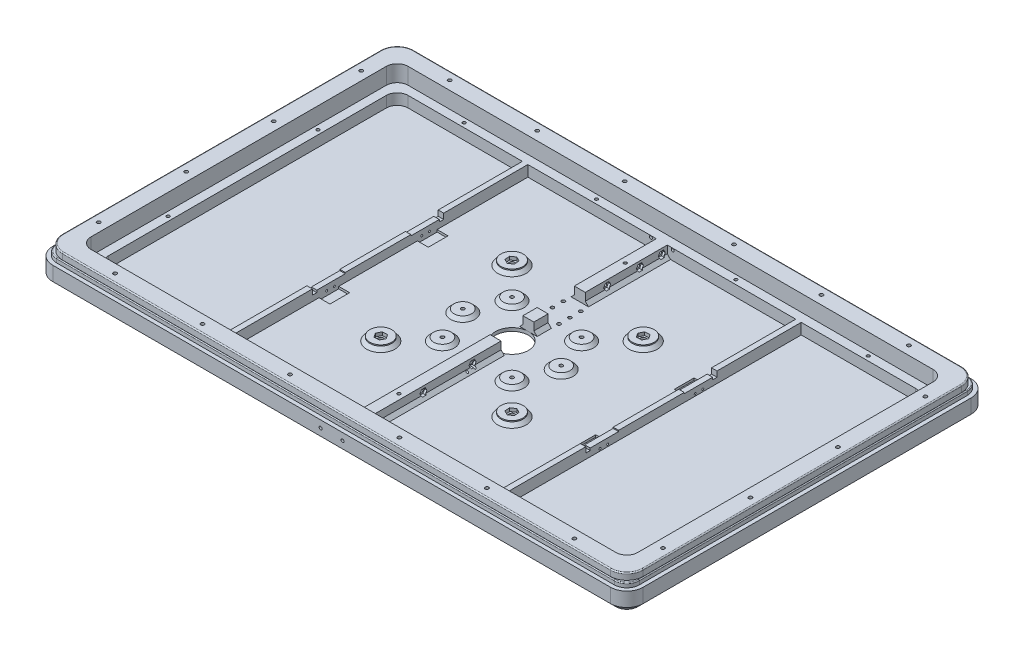
SolidWorks part; units mm, degrees
ref_plane "Front Plane" through (0, 0, 0) normal (0, 0, 1) x (1, 0, 0)
ref_plane "Top Plane" through (0, 0, 0) normal (0, 1, 0) x (1, 0, 0)
ref_plane "Right Plane" through (0, 0, 0) normal (1, 0, 0) x (0, 0, -1)
sketch "Sketch1" plane through (0, 0, 0) normal (0, 1, 0) x (1, 0, 0)
  line L1 (-270, -165) -> (270, -165)
  line L2 (-270, -165) -> (-270, 165)
  line L3 (-270, 165) -> (270, 165)
  line L4 (270, -165) -> (270, 165)
  line L5 (-270, -165) -> (270, 165) construction
  line L6 (-270, 165) -> (270, -165) construction
  point P0 (0, 0)
  dimension "D1" = 540
  dimension "D2" = 330
extrude "Boss-Extrude1" add sketch "Sketch1" along normal blind 3
sketch "Sketch2" plane through (0, 3, 0) normal (0, 1, 0) x (1, 0, 0)
  line L0 (250, 145) -> (-250, 145)
  line L1 (270, -165) -> (-270, -165)
  line L2 (270, -165) -> (270, 165)
  line L3 (270, 165) -> (-270, 165)
  line L4 (-270, -165) -> (-270, 165)
  line L5 (270, -165) -> (-270, 165) construction
  line L6 (270, 165) -> (-270, -165) construction
  line L7 (-250, -145) -> (-250, 145)
  line L8 (250, -145) -> (-250, -145)
  line L9 (250, -145) -> (250, 145)
  point P0 (0, 0)
  dimension "D1" = 20
  dimension "D2" = 540
extrude "Boss-Extrude2" add sketch "Sketch2" along normal blind 25 contours L0 L7 L8 L9 | L2 L1 L4 L3
fillet "Fillet1" radius 15 4 edges at (-270, 14, -165) (-270, 14, 165) (270, 14, 165) (270, 14, -165)
sketch "Sketch4" plane through (0, 28, 0) normal (0, 1, 0) x (1, 0, 0)
  line L0 (-270, 0) -> (-258, 0) construction
  line L1 (-270, -150) -> (-270, 150) construction
  line L2 (-258, 0) -> (-258, 40) construction
  line L3 (-258, 40) -> (-258, 120) construction
  line L4 (0, 0) -> (0, 145) construction
  line L5 (250, 145) -> (-250, 145) construction
  line L6 (0, 165) -> (0, 153) construction
  line L7 (255, 165) -> (-255, 165) construction
  line L8 (0, 153) -> (-50, 153) construction
  line L9 (-50, 153) -> (-130, 153) construction
  line L10 (-130, 153) -> (-210, 153) construction
  line L11 (130, 153) -> (210, 153) construction
  line L12 (50, 153) -> (130, 153) construction
  line L13 (258, 40) -> (258, 120) construction
  line L14 (0, 0) -> (78.1952, 0) construction
  line L15 (258, -40) -> (258, -120) construction
  line L16 (50, -153) -> (130, -153) construction
  line L17 (130, -153) -> (210, -153) construction
  line L18 (-130, -153) -> (-210, -153) construction
  line L19 (-50, -153) -> (-130, -153) construction
  line L20 (0, -153) -> (-50, -153) construction
  line L21 (0, -165) -> (0, -153) construction
  line L22 (-258, -40) -> (-258, -120) construction
  circle A0 centre (-258, 120) radius 1.6
  circle A1 centre (-258, 40) radius 1.6
  circle A2 centre (-210, 153) radius 1.6
  circle A3 centre (-130, 153) radius 1.6
  circle A4 centre (-50, 153) radius 1.6
  circle A5 centre (50, 153) radius 1.6
  circle A6 centre (130, 153) radius 1.6
  circle A7 centre (210, 153) radius 1.6
  circle A8 centre (258, 40) radius 1.6
  circle A9 centre (258, 120) radius 1.6
  circle A10 centre (258, -120) radius 1.6
  circle A11 centre (258, -40) radius 1.6
  circle A12 centre (210, -153) radius 1.6
  circle A13 centre (130, -153) radius 1.6
  circle A14 centre (50, -153) radius 1.6
  circle A15 centre (-50, -153) radius 1.6
  circle A16 centre (-130, -153) radius 1.6
  circle A17 centre (-210, -153) radius 1.6
  circle A18 centre (-258, -40) radius 1.6
  circle A19 centre (-258, -120) radius 1.6
  dimension "D1" = 50
  dimension "D2" = 80
  dimension "D3" = 80
  dimension "D4" = 12
  dimension "D5" = 12
  dimension "D6" = 40
  dimension "D7" = 80
extrude "Cut-Extrude1" cut sketch "Sketch4" against normal up to surface (28 mm away) up to face at (0, 0, 0)
sketch "Sketch5" plane through (0, 3, 0) normal (0, 1, 0) x (1, 0, 0)
  circle A0 centre (0, 0) radius 15
  dimension "D1" = 30
extrude "Cut-Extrude2" cut sketch "Sketch5" against normal up to surface (3 mm away) up to face at (-130, 0, 151.4)
chamfer "Chamfer1" distance 5 angle 45 8 edges at (270, 0, 0) (0, 0, -165) (0, 0, 165) (265.6066, 0, -160.6066) (265.6066, 0, 160.6066) (-265.6066, 0, -160.6066) (-265.6066, 0, 160.6066) (-270, 0, 0)
sketch "Sketch7" plane through (0, 0, 0) normal (0, -1, 0) x (1, 0, 0)
  line L1 (-60, -60) -> (60, -60) construction
  line L2 (-60, -60) -> (-60, 60) construction
  line L3 (-60, 60) -> (60, 60) construction
  line L4 (60, -60) -> (60, 60) construction
  line L5 (-60, -60) -> (60, 60) construction
  line L6 (-60, 60) -> (60, -60) construction
  circle A0 centre (-60, 60) radius 2.6
  circle A1 centre (60, 60) radius 2.6
  circle A2 centre (60, -60) radius 2.6
  circle A3 centre (-60, -60) radius 2.6
  point P0 (0, 0)
  dimension "D1" = 120
  dimension "D2" = 120
extrude "Cut-Extrude3" cut sketch "Sketch7" against normal up to surface (3 mm away) up to face at (0, 3, 15)
sketch "Sketch9" plane through (0, 0, 0) normal (0, -1, 0) x (1, 0, 0)
  line L0 (0, 0) -> (45, 0) construction
  line L1 (-31.8198, -31.8198) -> (31.8198, -31.8198) construction
  line L2 (-31.8198, -31.8198) -> (-31.8198, 31.8198) construction
  line L3 (-31.8198, 31.8198) -> (31.8198, 31.8198) construction
  line L4 (31.8198, -31.8198) -> (31.8198, 31.8198) construction
  line L5 (-31.8198, -31.8198) -> (31.8198, 31.8198) construction
  line L6 (-31.8198, 31.8198) -> (31.8198, -31.8198) construction
  line L7 (0, 0) -> (0, -31.8198) construction
  circle A0 centre (-31.8198, 31.8198) radius 1.6
  circle A1 centre (31.8198, 31.8198) radius 1.6
  circle A2 centre (31.8198, -31.8198) radius 1.6
  circle A3 centre (-31.8198, -31.8198) radius 1.6
  circle A4 centre (45, 0) radius 1.6
  circle A5 centre (-45, 0) radius 1.6
  point P0 (0, 0)
  dimension "D3" = 45
  dimension "D1" = 90
  dimension "D2" = 90
extrude "Cut-Extrude4" cut sketch "Sketch9" against normal blind 47
sketch "Sketch17" plane through (0, 28, 0) normal (0, 1, 0) x (1, 0, 0)
  line L0 (0, 0) -> (0, 165) construction
  line L1 (265, 165) -> (-265, 165) construction
sketch "Sketch18" plane through (0, 28, 0) normal (0, 1, 0) x (1, 0, 0)
  line L0 (0, 165) -> (0, -165) construction
  line L1 (265, 165) -> (-265, 165) construction
  line L2 (265, -165) -> (-265, -165) construction
sketch "Sketch19" plane through (0, 28, 0) normal (0, 1, 0) x (1, 0, 0)
  line L0 (250.5, 160.5) -> (-250.5, 160.5)
  line L1 (255, -165) -> (-255, -165)
  line L2 (270, -150) -> (270, 150)
  line L3 (255, 165) -> (-255, 165)
  line L4 (-270, -150) -> (-270, 150)
  line L5 (270, -165) -> (-270, 165) construction
  line L6 (270, 165) -> (-270, -165) construction
  line L7 (-265.5, -145.5) -> (-265.5, 145.5)
  line L8 (250.5, -160.5) -> (-250.5, -160.5)
  line L9 (265.5, -145.5) -> (265.5, 145.5)
  line L10 (255, 160.5) -> (-255, 160.5) construction
  line L11 (-265.5, -150) -> (-265.5, 150) construction
  line L12 (265.5, -150) -> (265.5, 150) construction
  line L13 (255, -160.5) -> (-255, -160.5) construction
  arc A0 (-270, -150) -> (-255, -165) centre (-255, -150) ccw
  arc A1 (255, -165) -> (270, -150) centre (255, -150) ccw
  arc A2 (270, 150) -> (255, 165) centre (255, 150) ccw
  arc A3 (-255, 165) -> (-270, 150) centre (-255, 150) ccw
  arc A4 (-255, 160.5) -> (-265.5, 150) centre (-255, 150) ccw construction
  arc A5 (-265.5, -150) -> (-255, -160.5) centre (-255, -150) ccw construction
  arc A6 (255, -160.5) -> (265.5, -150) centre (255, -150) ccw construction
  arc A7 (265.5, 150) -> (255, 160.5) centre (255, 150) ccw construction
  arc A8 (-250.5, 160.5) -> (-265.5, 145.5) centre (-250.5, 145.5) ccw
  arc A9 (265.5, 145.5) -> (250.5, 160.5) centre (250.5, 145.5) ccw
  arc A10 (265.5, -145.5) -> (250.5, -160.5) centre (250.5, -145.5) cw
  arc A11 (-250.5, -160.5) -> (-265.5, -145.5) centre (-250.5, -145.5) cw
  point P0 (0, 0)
  dimension "D3" = 15
  dimension "D5" = 15
  dimension "D6" = 15
  dimension "D7" = 15
  dimension "D8" = 15
  dimension "D1" = 330
  dimension "D2" = 540
  dimension "D4" = 4.5
extrude "Cut-Extrude5" cut sketch "Sketch19" against normal blind 10
fillet "Fillet2" radius 1 8 edges at (265.5, 28, 0) (0, 28, 160.5) (-265.5, 28, 0) (0, 28, -160.5) (261.1066, 28, -156.1066) (261.1066, 28, 156.1066) (-261.1066, 28, 156.1066) (-261.1066, 28, -156.1066)
sketch "Sketch20" plane through (0, 18, 0) normal (0, 1, 0) x (1, 0, 0)
  line L0 (0, 165) -> (0, -165) construction
  line L1 (-255, 165) -> (255, 165) construction
  line L2 (-270, 150) -> (-270, -150) construction
  line L3 (-255, -165) -> (255, -165) construction
  line L4 (270, 150) -> (270, -150) construction
  line L5 (-270, 165) -> (270, -165) construction
  line L6 (-270, -165) -> (270, 165) construction
  line L7 (-255, 161.4) -> (255, 161.4)
  line L8 (266.4, 150) -> (266.4, -150)
  line L9 (-255, -161.4) -> (255, -161.4)
  line L10 (-266.4, 150) -> (-266.4, -150)
  line L11 (-255, 157.9) -> (255, 157.9)
  line L12 (262.9, 150) -> (262.9, -150)
  line L13 (-255, -157.9) -> (255, -157.9)
  line L14 (-262.9, 150) -> (-262.9, -150)
  arc A0 (-270, -150) -> (-255, -165) centre (-255, -150) ccw construction
  arc A1 (270, -150) -> (255, -165) centre (255, -150) cw construction
  arc A2 (270, 150) -> (255, 165) centre (255, 150) ccw construction
  arc A3 (-255, 165) -> (-270, 150) centre (-255, 150) ccw construction
  arc A4 (266.4, 150) -> (255, 161.4) centre (255, 150) ccw
  arc A5 (266.4, -150) -> (255, -161.4) centre (255, -150) cw
  arc A6 (-266.4, -150) -> (-255, -161.4) centre (-255, -150) ccw
  arc A7 (-255, 161.4) -> (-266.4, 150) centre (-255, 150) ccw
  arc A8 (262.9, 150) -> (255, 157.9) centre (255, 150) ccw
  arc A9 (262.9, -150) -> (255, -157.9) centre (255, -150) cw
  arc A10 (-262.9, -150) -> (-255, -157.9) centre (-255, -150) ccw
  arc A11 (-255, 157.9) -> (-262.9, 150) centre (-255, 150) ccw
  point P0 (0, 0)
  dimension "D3" = 15
  dimension "D1" = 330
  dimension "D2" = 540
  dimension "D4" = 3.6
  dimension "D5" = 3.5
extrude "Boss-Extrude3" add sketch "Sketch20" along normal blind 4
fillet "Fillet4" radius 0.8 8 edges at (263.061, 22, -158.061) (266.4, 22, 0) (263.061, 22, 158.061) (0, 22, 161.4) (-263.061, 22, 158.061) (-266.4, 22, 0) (-263.061, 22, -158.061) (0, 22, -161.4)
sketch "Sketch23" plane through (0, 3, 0) normal (0, 1, 0) x (1, 0, 0)
  line L0 (250, 145) -> (-250, 145) construction
  line L1 (-5, -145) -> (5, -145)
  line L2 (-5, -145) -> (-5, 145)
  line L3 (-5, 145) -> (5, 145)
  line L4 (5, -145) -> (5, 145)
  line L5 (-5, -145) -> (5, 145) construction
  line L6 (-5, 145) -> (5, -145) construction
  line L7 (0, 0) -> (250, 0) construction
  line L8 (-5, -15) -> (5, -15)
  line L9 (-5, -15) -> (-5, 15)
  line L10 (-5, 15) -> (5, 15)
  line L11 (5, -15) -> (5, 15)
  line L12 (-5, -15) -> (5, 15) construction
  line L13 (-5, 15) -> (5, -15) construction
  line L14 (250, -145) -> (250, 145) construction
  line L15 (250, 145) -> (-250, 145) construction
  line L16 (122.5, -145) -> (127.5, -145)
  line L17 (122.5, -145) -> (122.5, 145)
  line L18 (122.5, 145) -> (127.5, 145)
  line L19 (127.5, -145) -> (127.5, 145)
  line L20 (122.5, -145) -> (127.5, 145) construction
  line L21 (122.5, 145) -> (127.5, -145) construction
  line L27 (0, 0) -> (0, 145) construction
  line L28 (-122.5, 145) -> (-127.5, 145)
  line L29 (-127.5, -145) -> (-127.5, 145)
  line L30 (-122.5, -145) -> (-127.5, -145)
  line L31 (-122.5, -145) -> (-122.5, 145)
  point P0 (0, 0)
  point P8 (0, 0)
  point P17 (125, 0)
  line M14 (-250, -145) -> (250, -145)
  line M16 (250, 145) -> (-250, 145)
  dimension "D1" = 30
  dimension "D2" = 10
  dimension "D3" = 5
extrude "Boss-Extrude4" add sketch "Sketch23" along normal blind 10 contours L2 L10 L4 M16 | L8 L2 L4 M14 | L17 L16 L19 L18 | L28 L29 L30 L31 region at (0, 3, 80) region at (0, 3, -80)
sketch "Sketch24" plane through (0, 3, 0) normal (0, 1, 0) x (1, 0, 0)
  line L0 (-242, 137) -> (242, 137)
  line L1 (-250, -145) -> (250, -145)
  line L2 (-250, -145) -> (-250, 145)
  line L3 (-250, 145) -> (250, 145)
  line L4 (250, -145) -> (250, 145)
  line L5 (-250, -145) -> (250, 145) construction
  line L6 (-250, 145) -> (250, -145) construction
  line L7 (242, -137) -> (242, 137)
  line L8 (-242, -137) -> (242, -137)
  line L9 (-242, -137) -> (-242, 137)
  point P0 (0, 0)
  dimension "D1" = 8
extrude "Boss-Extrude5" add sketch "Sketch24" along normal up to surface (10 mm away) up to face at (-125, 13, 0)
sketch "Sketch25" plane through (127.5, 0, 0) normal (1, 0, 0) x (0, 0, -1)
  line L0 (0, 5) -> (0, 13) construction
  line L1 (-150, 5) -> (150, 5) construction
  line L2 (-145, 13) -> (145, 13) construction
  line L3 (0, 13) -> (0, 5) construction
  line L4 (0, 5) -> (-40, 5) construction
  line L5 (-40, 5) -> (-47, 5) construction
  circle A0 centre (-47, 5) radius 0.9
  circle A1 centre (-40, 5) radius 0.9
  circle A2 centre (47, 5) radius 0.9
  circle A3 centre (40, 5) radius 0.9
  dimension "D1" = 8
  dimension "D2" = 40
  dimension "D3" = 7
extrude "Cut-Extrude6" cut sketch "Sketch25" against normal up to surface (255 mm away) up to face at (-127.5, 8, 0)
sketch "Sketch26" plane through (0, 3, 0) normal (0, 1, 0) x (1, 0, 0)
  line L0 (0, 0) -> (-122.5, 0) construction
  line L1 (-122.5, -137) -> (-122.5, 137) construction
  line L2 (-122.5, 0) -> (-122.5, 36) construction
  line L3 (-122.5, -137) -> (-122.5, 137) construction
  line L4 (-122.5, -54) -> (-112.5, -54)
  line L5 (-122.5, 36) -> (-112.5, 36)
  line L6 (-122.5, 36) -> (-122.5, 54)
  line L7 (-122.5, 54) -> (-112.5, 54)
  line L8 (-112.5, 36) -> (-112.5, 54)
  line L9 (-122.5, -36) -> (-112.5, -36)
  line L10 (-122.5, -36) -> (-122.5, -54)
  line L11 (-112.5, -36) -> (-112.5, -54)
  line L12 (0, 0) -> (0, 165) construction
  line L13 (122.5, -36) -> (122.5, -54)
  line L14 (122.5, -36) -> (112.5, -36)
  line L15 (112.5, -36) -> (112.5, -54)
  line L16 (122.5, -54) -> (112.5, -54)
  line L17 (122.5, 54) -> (112.5, 54)
  line L18 (112.5, 36) -> (112.5, 54)
  line L19 (122.5, 36) -> (112.5, 36)
  line L20 (122.5, 36) -> (122.5, 54)
  point P11 (-112.5, 45)
  dimension "D1" = 36
  dimension "D2" = 10
extrude "Cut-Extrude7" cut sketch "Sketch26" against normal blind 2
sketch "Sketch27" plane through (0, 13, 0) normal (0, 1, 0) x (1, 0, 0)
  line L0 (0, 0) -> (0, 165) construction
  line L1 (-122.5, 0) -> (-127.5, 0) construction
  line L2 (-122.5, -36) -> (-122.5, 36) construction
  line L3 (-127.5, -137) -> (-127.5, 137) construction
  line L4 (-127.5, -137) -> (-127.5, 137) construction
  line L5 (-122.5, -60) -> (-127.5, -60)
  line L6 (-122.5, -60) -> (-122.5, -30)
  line L7 (-122.5, 60) -> (-127.5, 60)
  line L8 (-127.5, -60) -> (-127.5, -30)
  line L9 (-122.5, -60) -> (-123.75, -30) construction
  line L10 (-122.5, 60) -> (-123.75, 30) construction
  line L11 (-127.5, 30) -> (-127.5, 60)
  line L12 (-127.5, -30) -> (-122.5, -30)
  line L14 (-127.5, 30) -> (-122.5, 30)
  line L16 (126.25, -30) -> (127.5, -60) construction
  line L17 (126.25, 30) -> (127.5, 60) construction
  line L18 (-126.25, 30) -> (-127.5, 60) construction
  line L19 (-126.25, -30) -> (-127.5, -60) construction
  line L20 (-122.5, 30) -> (-122.5, 60)
  line L21 (122.5, 60) -> (123.75, 30) construction
  line L22 (122.5, -60) -> (123.75, -30) construction
  line L23 (122.5, 0) -> (127.5, 0) construction
  line L24 (122.5, 30) -> (122.5, 60)
  line L25 (127.5, 30) -> (122.5, 30)
  line L26 (127.5, -30) -> (122.5, -30)
  line L27 (127.5, 30) -> (127.5, 60)
  line L28 (127.5, -60) -> (127.5, -30)
  line L29 (122.5, 60) -> (127.5, 60)
  line L30 (122.5, -60) -> (122.5, -30)
  line L31 (122.5, -60) -> (127.5, -60)
  point P10 (-125, 0)
  point P17 (-125, 0)
  point P40 (125, 0)
  dimension "D1" = 120
  dimension "D2" = 60
extrude "Cut-Extrude8" cut sketch "Sketch27" against normal blind 3
sketch "Sketch28" plane through (0, 13, 0) normal (0, 1, 0) x (1, 0, 0)
  line L1 (-127.5, 30) -> (-122.5, 30)
  line L2 (-127.5, 30) -> (-127.5, -30)
  line L3 (-127.5, -30) -> (-122.5, -30)
  line L4 (-122.5, 30) -> (-122.5, -30)
  line L5 (122.5, 30) -> (127.5, 30)
  line L6 (122.5, 30) -> (122.5, -30)
  line L7 (122.5, -30) -> (127.5, -30)
  line L8 (127.5, 30) -> (127.5, -30)
extrude "Cut-Extrude9" cut sketch "Sketch28" against normal blind 2
sketch "Sketch29" plane through (0, 10, 0) normal (0, 1, 0) x (1, 0, 0)
  line L0 (-122.5, 30) -> (-122.5, 60) construction
  line L1 (-127.5, 60) -> (-122.5, 60)
  line L2 (-127.5, 60) -> (-127.5, 56)
  line L3 (-127.5, 56) -> (-122.5, 56)
  line L4 (-122.5, 60) -> (-122.5, 56)
  line L5 (-122.5, -60) -> (-122.5, -30) construction
  line L6 (-127.5, -60) -> (-122.5, -60)
  line L7 (-127.5, -60) -> (-127.5, -56)
  line L8 (-127.5, -56) -> (-122.5, -56)
  line L9 (-122.5, -60) -> (-122.5, -56)
  line L10 (127.5, -60) -> (127.5, -30) construction
  line L11 (122.5, -60) -> (127.5, -60)
  line L12 (122.5, -60) -> (122.5, -56)
  line L13 (122.5, -56) -> (127.5, -56)
  line L14 (127.5, -60) -> (127.5, -56)
  line L15 (127.5, -137) -> (127.5, 137) construction
  line L16 (122.5, 60) -> (127.5, 60)
  line L17 (122.5, 60) -> (122.5, 56)
  line L18 (122.5, 56) -> (127.5, 56)
  line L19 (127.5, 60) -> (127.5, 56)
extrude "Cut-Extrude10" cut sketch "Sketch29" against normal blind 2
sketch "Sketch31" plane through (0, 13, 0) normal (0, 1, 0) x (1, 0, 0)
  line L0 (0, 165) -> (0, 45) construction
  line L1 (255, 165) -> (-255, 165) construction
  line L3 (-8, 62) -> (8, 62)
  line L4 (-8, 62) -> (-8, 28)
  line L5 (-8, 28) -> (8, 28)
  line L6 (8, 62) -> (8, 28)
  line L7 (-8, 62) -> (8, 28) construction
  line L8 (-8, 28) -> (8, 62) construction
  dimension "D1" = 120
  dimension "D2" = 34
  dimension "D3" = 16
  dimension "D4" = 16
sketch "Sketch32" plane through (-270, 0, 0) normal (-1, 0, 0) x (0, 0, 1)
  line L0 (-30, 13) -> (-30, 18) construction
  line L1 (-62, 13) -> (-28, 13) construction
  line L2 (-150, 18) -> (150, 18) construction
  line L3 (-30, 18) -> (-30, 51) construction
extrude "Boss-Extrude6" add sketch "Sketch31" along normal blind 53 and the other way up to surface (10 mm away) other way up to face at (-60, 3, 57.4)
fillet "Fillet5" radius 15 2 edges at (0, 66, -28) (0, 66, -62)
sketch "Sketch34" plane through (-8, 0, 0) normal (-1, 0, 0) x (0, 0, 1)
  line L0 (-165, 18) -> (-45, 18) construction
  line L1 (-150, 18) -> (150, 18) construction
  line L2 (-45, 18) -> (-45, 53) construction
  circle A0 centre (-45, 53) radius 3
  dimension "D3" = 6
  dimension "D1" = 120
  dimension "D2" = 35
extrude "Cut-Extrude11" cut sketch "Sketch34" against normal blind 53
sketch "Sketch35" plane through (0, 3, 0) normal (0, 1, 0) x (1, 0, 0)
  circle A0 centre (-31.8198, 31.8198) radius 1.6
  circle A1 centre (-31.8198, 31.8198) radius 8
  circle A2 centre (31.8198, 31.8198) radius 1.6
  circle A3 centre (31.8198, 31.8198) radius 8
  circle A4 centre (31.8198, -31.8198) radius 1.6
  circle A5 centre (31.8198, -31.8198) radius 8
  circle A6 centre (-31.8198, -31.8198) radius 1.6
  circle A7 centre (-31.8198, -31.8198) radius 8
  circle A8 centre (-45, 0) radius 8
  circle A9 centre (45, 0) radius 8
  circle A10 centre (45, 0) radius 1.6
  circle A11 centre (-45, 0) radius 1.6
  point P16 (0, 0)
  dimension "D1" = 16
  dimension "D2" = 3.2
  dimension "D3" = 4
extrude "Boss-Extrude7" add sketch "Sketch35" along normal blind 3
chamfer "Chamfer2" distance 3 angle 45 6 edges at (31.8198, 3, 23.8198) (-31.8198, 3, 23.8198) (-31.8198, 3, -39.8198) (31.8198, 3, -39.8198) (45, 3, -8) (-45, 3, -8)
sketch "Sketch37" plane through (0, 66, 0) normal (0, 1, 0) x (1, 0, 0)
  line L0 (0, 47) -> (0, 43) construction
  line L1 (8, 47) -> (-8, 47) construction
  line L2 (-8, 43) -> (8, 43) construction
  line L4 (-8, 28) -> (8, 28)
  line L5 (-8, 28) -> (-8, 62)
  line L6 (-8, 62) -> (8, 62)
  line L7 (8, 28) -> (8, 62)
  line L8 (-8, 28) -> (8, 62) construction
  line L9 (-8, 62) -> (8, 28) construction
  point P6 (0, 45)
extrude "Cut-Extrude12" cut sketch "Sketch37" against normal up to surface (63 mm away) up to face at (-45, 3, -11)
sketch "Sketch38" plane through (0, 3, 0) normal (0, 1, 0) x (1, 0, 0)
  line L0 (0, 62) -> (0, 28) construction
  line L1 (5, 62) -> (-5, 62) construction
  line L2 (-5, 28) -> (5, 28) construction
  line L3 (0, 28) -> (0, 45) construction
  line L4 (0, 45) -> (8, 45) construction
  line L5 (8, 45) -> (8, 55) construction
  circle A0 centre (8, 55) radius 1.6
  circle A1 centre (8, 35) radius 1.6
  circle A2 centre (-8, 35) radius 1.6
  circle A3 centre (-8, 55) radius 1.6
  circle A4 centre (8, 45) radius 1.5
  circle A5 centre (-8, 45) radius 1.5
  dimension "D2" = 10
  dimension "D1" = 8
extrude "Cut-Extrude13" cut sketch "Sketch38" against normal blind 90
chamfer "Chamfer3" distance 3 angle 45 6 edges at (-5, 3, 76) (-5, 3, -21.5) (5, 3, -21.5) (5, 3, 76) (5, 3, -99.5) (-5, 3, -99.5)
sketch "Sketch39" plane through (0, 13, 0) normal (0, 1, 0) x (1, 0, 0)
  line L0 (-242, 0) -> (-242, 137) construction
  line L1 (-242, 137) -> (-242, -137) construction
  line L2 (-242, 137) -> (-242, 68.5) construction
  line L3 (-242, 68.5) -> (-250, 68.5) construction
  line L4 (-250, -145) -> (-250, 145) construction
  line L5 (-184.75, 137) -> (-184.75, 145) construction
  line L6 (-127.5, 137) -> (-242, 137) construction
  line L7 (250, 145) -> (-250, 145) construction
  line L8 (-63.75, 137) -> (-63.75, 145) construction
  line L10 (-5, 137) -> (-122.5, 137) construction
  line L11 (250, 145) -> (-250, 145) construction
  line L12 (0, 0) -> (0, 145) construction
  line L13 (63.75, 137) -> (63.75, 145) construction
  line L14 (184.75, 137) -> (184.75, 145) construction
  line L15 (242, 68.5) -> (250, 68.5) construction
  line L16 (242, 137) -> (242, 68.5) construction
  line L17 (0, 62) -> (0, 145) construction
  line L18 (5, 62) -> (-5, 62) construction
  line L19 (0, 0) -> (250, 0) construction
  line L20 (250, -145) -> (250, 145) construction
  line L21 (0, -62) -> (0, -145) construction
  line L22 (242, -137) -> (242, -68.5) construction
  line L23 (242, -68.5) -> (250, -68.5) construction
  line L24 (184.75, -137) -> (184.75, -145) construction
  line L25 (63.75, -137) -> (63.75, -145) construction
  line L26 (-63.75, -137) -> (-63.75, -145) construction
  line L27 (-184.75, -137) -> (-184.75, -145) construction
  line L28 (-242, -68.5) -> (-250, -68.5) construction
  line L29 (-242, -137) -> (-242, -68.5) construction
  circle A0 centre (-246, 68.5) radius 1.4
  circle A1 centre (-184.75, 141) radius 1.4
  circle A2 centre (-63.75, 141) radius 1.4
  circle A3 centre (63.75, 141) radius 1.4
  circle A4 centre (184.75, 141) radius 1.4
  circle A5 centre (246, 68.5) radius 1.4
  circle A6 centre (0, 103.5) radius 1.4
  circle A7 centre (0, -103.5) radius 1.4
  circle A8 centre (246, -68.5) radius 1.4
  circle A9 centre (184.75, -141) radius 1.4
  circle A10 centre (63.75, -141) radius 1.4
  circle A11 centre (-63.75, -141) radius 1.4
  circle A12 centre (-184.75, -141) radius 1.4
  circle A13 centre (-246, -68.5) radius 1.4
extrude "Cut-Extrude14" cut sketch "Sketch39" against normal blind 8
fillet "Fillet6" radius 10 4 edges at (-242, 8, -137) (-242, 8, 137) (242, 8, 137) (242, 8, -137)
fillet "Fillet7" radius 10 4 edges at (250, 20.5, 145) (250, 20.5, -145) (-250, 20.5, 145) (-250, 20.5, -145)
sketch "Sketch41" plane through (0, 0, 0) normal (1, 0, 0) x (0, 0, -1)
  line L0 (165, 11.5) -> (153, 11.5) construction
  line L1 (165, 18) -> (165, 5) construction
  line L2 (0, 0) -> (0, 98.4706) construction
  circle A0 centre (153, 11.5) radius 5
  circle A1 centre (-153, 11.5) radius 5
  dimension "D1" = 12
extrude "Cut-Extrude15" cut sketch "Sketch41" against normal blind 30 and the other way blind 30
sketch "Sketch42" plane through (5, 0, 0) normal (1, 0, 0) x (0, 0, -1)
  line L0 (-132, 3) -> (-132, 13) construction
  line L1 (-127, 3) -> (-137, 3) construction
  line L2 (-135, 13) -> (135, 13) construction
  line L3 (-102.1, 13) -> (-69.9, 13) construction
  line L4 (-69.9, 13) -> (-86, 13) construction
  line L5 (-86, 13) -> (-86, 3) construction
  line L6 (-127, 3) -> (127, 3) construction
  line L7 (-67.1, 13) -> (-15, 13) construction
  line L8 (-15, 13) -> (-41.05, 13) construction
  line L9 (-41.05, 13) -> (-41.05, 3) construction
  line L10 (145, 13) -> (145, 3) construction
  line L11 (145, 3) -> (145, 8) construction
  line L12 (145, 8) -> (132, 8) construction
  line L13 (132, 8) -> (112, 8) construction
  line L14 (112, 8) -> (82, 8) construction
  circle A0 centre (112, 8) radius 1.6
  circle A1 centre (132, 8) radius 1.6
  circle A2 centre (82, 8) radius 1.6
  circle A3 centre (-86, 8) radius 1.6
  circle A4 centre (-132, 8) radius 1.6
  circle A5 centre (-41.05, 8) radius 1.6
  dimension "D1" = 30
  dimension "D2" = 20
  dimension "D3" = 13
extrude "Cut-Extrude16" cut sketch "Sketch42" against normal blind 30 and the other way blind 10
sketch "Sketch43" plane through (5, 0, 0) normal (1, 0, 0) x (0, 0, -1)
  line L0 (-87.6166, 10.8) -> (-89.2332, 8)
  line L1 (-128.7668, 8) -> (-130.3834, 10.8)
  line L2 (-130.3834, 10.8) -> (-133.6166, 10.8)
  line L3 (-133.6166, 10.8) -> (-135.2332, 8)
  line L4 (-135.2332, 8) -> (-133.6166, 5.2)
  line L5 (-133.6166, 5.2) -> (-130.3834, 5.2)
  line L6 (-130.3834, 5.2) -> (-128.7668, 8)
  line L7 (-89.2332, 8) -> (-87.6166, 5.2)
  line L8 (-87.6166, 5.2) -> (-84.3834, 5.2)
  line L9 (-82.7668, 8) -> (-84.3834, 10.8)
  line L10 (-84.3834, 10.8) -> (-87.6166, 10.8)
  line L11 (-84.3834, 5.2) -> (-82.7668, 8)
  line L12 (-37.8168, 8) -> (-39.4334, 10.8)
  line L13 (-39.4334, 5.2) -> (-37.8168, 8)
  line L14 (-42.6666, 10.8) -> (-44.2832, 8)
  line L15 (-39.4334, 10.8) -> (-42.6666, 10.8)
  line L16 (-42.6666, 5.2) -> (-39.4334, 5.2)
  line L17 (-44.2832, 8) -> (-42.6666, 5.2)
  line L18 (85.2332, 8) -> (83.6166, 10.8)
  line L19 (83.6166, 5.2) -> (85.2332, 8)
  line L20 (80.3834, 10.8) -> (78.7668, 8)
  line L21 (83.6166, 10.8) -> (80.3834, 10.8)
  line L22 (80.3834, 5.2) -> (83.6166, 5.2)
  line L23 (78.7668, 8) -> (80.3834, 5.2)
  line L24 (115.2332, 8) -> (113.6166, 10.8)
  line L25 (113.6166, 5.2) -> (115.2332, 8)
  line L26 (110.3834, 10.8) -> (108.7668, 8)
  line L27 (113.6166, 10.8) -> (110.3834, 10.8)
  line L28 (110.3834, 5.2) -> (113.6166, 5.2)
  line L29 (108.7668, 8) -> (110.3834, 5.2)
  line L30 (82, 8) -> (112, 8) construction
  line L31 (112, 8) -> (132, 8) construction
  line L32 (130.3834, 10.8) -> (128.7668, 8)
  line L33 (130.3834, 5.2) -> (133.6166, 5.2)
  line L34 (135.2332, 8) -> (133.6166, 10.8)
  line L35 (133.6166, 10.8) -> (130.3834, 10.8)
  line L36 (128.7668, 8) -> (130.3834, 5.2)
  line L37 (133.6166, 5.2) -> (135.2332, 8)
  circle A0 centre (-132, 8) radius 2.8 construction
  circle A1 centre (-86, 8) radius 2.8 construction
  circle A2 centre (-41.05, 8) radius 2.8 construction
  circle A3 centre (82, 8) radius 2.8 construction
  circle A4 centre (112, 8) radius 2.8 construction
  circle A5 centre (132, 8) radius 2.8 construction
  dimension "D1" = 5.6
extrude "Cut-Extrude17" cut sketch "Sketch43" against normal blind 2 and the other way blind 17
sketch "Sketch45" plane through (0, 3, 0) normal (0, 1, 0) x (1, 0, 0)
  circle A0 centre (-60, 60) radius 10
  circle A1 centre (-60, 60) radius 2.6
  circle A2 centre (60, 60) radius 10
  circle A3 centre (60, 60) radius 2.6
  circle A4 centre (60, -60) radius 10
  circle A5 centre (60, -60) radius 2.6
  circle A6 centre (-60, -60) radius 10
  circle A7 centre (-60, -60) radius 2.6
  point P16 (0, 0)
  dimension "D1" = 20
  dimension "D2" = 4
extrude "Boss-Extrude8" add sketch "Sketch45" along normal blind 4
chamfer "Chamfer4" distance 3 angle 45 4 edges at (-60, 3, -70) (60, 3, -70) (-60, 3, 50) (60, 3, 50)
sketch "Sketch48" plane through (0, 7, 0) normal (0, 1, 0) x (1, 0, 0)
  line L0 (62.567, 56.091) -> (64.6688, 60.2686)
  line L1 (-56.091, 62.567) -> (-60.2686, 64.6688)
  line L2 (-60.2686, 64.6688) -> (-64.1776, 62.1018)
  line L3 (-64.1776, 62.1018) -> (-63.909, 57.433)
  line L4 (-63.909, 57.433) -> (-59.7314, 55.3312)
  line L5 (-59.7314, 55.3312) -> (-55.8224, 57.8982)
  line L6 (-55.8224, 57.8982) -> (-56.091, 62.567)
  line L7 (64.6688, 60.2686) -> (62.1018, 64.1776)
  line L8 (62.1018, 64.1776) -> (57.433, 63.909)
  line L9 (57.433, 63.909) -> (55.3312, 59.7314)
  line L10 (55.3312, 59.7314) -> (57.8982, 55.8224)
  line L11 (57.8982, 55.8224) -> (62.567, 56.091)
  line L12 (56.091, -62.567) -> (60.2686, -64.6688)
  line L13 (60.2686, -64.6688) -> (64.1776, -62.1018)
  line L14 (64.1776, -62.1018) -> (63.909, -57.433)
  line L15 (63.909, -57.433) -> (59.7314, -55.3312)
  line L16 (59.7314, -55.3312) -> (55.8224, -57.8982)
  line L17 (55.8224, -57.8982) -> (56.091, -62.567)
  line L18 (-62.567, -56.091) -> (-64.6688, -60.2686)
  line L19 (-64.6688, -60.2686) -> (-62.1018, -64.1776)
  line L20 (-62.1018, -64.1776) -> (-57.433, -63.909)
  line L21 (-57.433, -63.909) -> (-55.3312, -59.7314)
  line L22 (-55.3312, -59.7314) -> (-57.8982, -55.8224)
  line L23 (-57.8982, -55.8224) -> (-62.567, -56.091)
  circle A0 centre (-60, 60) radius 4.05 construction
  circle A1 centre (60, 60) radius 4.05 construction
  circle A2 centre (60, -60) radius 4.05 construction
  circle A3 centre (-60, -60) radius 4.05 construction
  point P36 (0, 0)
  dimension "D1" = 8.1
  dimension "D2" = 4
extrude "Cut-Extrude18" cut sketch "Sketch48" against normal blind 3
sketch "Sketch49" plane through (0, 0, 0) normal (0, -1, 0) x (1, 0, 0)
  circle A0 centre (0, 0) radius 60
sketch "Sketch50" plane through (0, 0, 0) normal (0, -1, 0) x (1, 0, 0)
  line L1 (-60, 60) -> (60, 60) construction
sketch "Sketch52" plane through (0, 0, 165) normal (0, 0, 1) x (1, 0, 0)
  line L0 (0, 5) -> (0, 18) construction
  line L1 (-255, 5) -> (255, 5) construction
  line L2 (-255, 18) -> (255, 18) construction
  line L3 (0, 18) -> (0, 11.5) construction
  line L4 (0, 11.5) -> (-10, 11.5) construction
  circle A0 centre (-10, 11.5) radius 1.35
  circle A1 centre (10, 11.5) radius 1.35
  dimension "D2" = 2.7
  dimension "D1" = 10
extrude "Cut-Extrude20" cut sketch "Sketch52" against normal up to surface (330 mm away) contours A0 | A1 region at (-10, 11.5, 165) up to face at (0, 11.5, -165)
sketch "Sketch53" plane through (0, 13, 0) normal (0, 1, 0) x (1, 0, 0)
  line L0 (0, 145) -> (0, 141) construction
  line L1 (-239, 145) -> (239, 145)
  line L2 (-250, 134) -> (-250, -134)
  line L3 (-239, -145) -> (239, -145)
  line L4 (250, 134) -> (250, -134)
  line L5 (-250, 145) -> (250, -145) construction
  line L6 (-250, -145) -> (250, 145) construction
  line L7 (0, 0) -> (0, 79.598) construction
  line L8 (0, 0) -> (95.4216, 0) construction
  line L10 (-125, 30) -> (-125, -30) construction
  line L11 (-122.5, 30) -> (-127.5, 30) construction
  line L12 (-122.5, -30) -> (-127.5, -30) construction
  line L13 (-125, -30) -> (125, -30) construction
  line L14 (127.5, -30) -> (122.5, -30) construction
  line L15 (125, -30) -> (125, 30) construction
  line L16 (127.5, 30) -> (122.5, 30) construction
  line L17 (0, 62) -> (0, 28) construction
  line L18 (-127.5, -70) -> (-122.5, -70)
  line L19 (-137.5, -60) -> (-137.5, 60)
  line L20 (-127.5, 70) -> (-122.5, 70)
  line L21 (-112.5, -60) -> (-112.5, 60)
  line L22 (-137.5, -70) -> (-112.5, 70) construction
  line L23 (-137.5, 70) -> (-112.5, -70) construction
  line L24 (122.5, -70) -> (127.5, -70)
  line L25 (112.5, -60) -> (112.5, 60)
  line L26 (122.5, 70) -> (127.5, 70)
  line L27 (137.5, -60) -> (137.5, 60)
  line L28 (112.5, -70) -> (137.5, 70) construction
  line L29 (112.5, 70) -> (137.5, -70) construction
  line L30 (5, 62) -> (-5, 62) construction
  line L31 (-5, 28) -> (5, 28) construction
  line L32 (8, 62) -> (-8, 62) construction
  line L33 (-5, 28) -> (5, 28)
  line L34 (-5, 28) -> (-5, 62)
  line L35 (-5, 62) -> (5, 62)
  line L36 (5, 28) -> (5, 62)
  line L37 (-5, 28) -> (5, 62) construction
  line L38 (-5, 62) -> (5, 28) construction
  arc A0 (-250, -134) -> (-239, -145) centre (-239, -134) ccw
  arc A1 (250, -134) -> (239, -145) centre (239, -134) cw
  arc A2 (250, 134) -> (239, 145) centre (239, 134) ccw
  arc A3 (-239, 145) -> (-250, 134) centre (-239, 134) ccw
  circle A6 centre (63.75, 141) radius 1.6
  circle A7 centre (184.75, 141) radius 1.6
  circle A8 centre (246, 68.5) radius 1.6
  circle A9 centre (0, 103.5) radius 1.4
  circle A10 centre (0, -103.5) radius 1.4
  arc A11 (137.5, 60) -> (127.5, 70) centre (127.5, 60) ccw
  arc A12 (122.5, 70) -> (112.5, 60) centre (122.5, 60) ccw
  arc A13 (137.5, -60) -> (127.5, -70) centre (127.5, -60) cw
  arc A14 (112.5, -60) -> (122.5, -70) centre (122.5, -60) ccw
  arc A15 (-112.5, -60) -> (-122.5, -70) centre (-122.5, -60) cw
  arc A16 (-127.5, -70) -> (-137.5, -60) centre (-127.5, -60) cw
  arc A17 (-112.5, 60) -> (-122.5, 70) centre (-122.5, 60) ccw
  arc A18 (-127.5, 70) -> (-137.5, 60) centre (-127.5, 60) ccw
  circle A19 centre (-246, 68.5) radius 1.6
  circle A20 centre (-184.75, 141) radius 1.6
  circle A21 centre (-63.75, 141) radius 1.6
  circle A22 centre (184.75, -141) radius 1.6
  circle A23 centre (246, -68.5) radius 1.6
  circle A24 centre (63.75, -141) radius 1.6
  circle A25 centre (-63.75, -141) radius 1.6
  circle A26 centre (-184.75, -141) radius 1.6
  circle A27 centre (-246, -68.5) radius 1.6
  point P0 (0, 0)
  point P47 (-125, 0)
  point P58 (125, 0)
  point P93 (0, 45)
  dimension "D3" = 11
  dimension "D4" = 140
  dimension "D8" = 10
  dimension "D1" = 290
  dimension "D2" = 500
  dimension "D5" = 140
  dimension "D6" = 25
  dimension "D7" = 25
  dimension "D9" = 10
  dimension "D10" = 34
sketch "Sketch54" plane through (0, 3, 0) normal (0, 1, 0) x (1, 0, 0)
  line L0 (0, 62) -> (0, 28) construction
  line L1 (8, 62) -> (-8, 62) construction
  line L2 (-8, 28) -> (8, 28) construction
  line L4 (-12.5, 28) -> (12.5, 28)
  line L5 (-12.5, 28) -> (-12.5, 62)
  line L6 (-12.5, 62) -> (12.5, 62)
  line L7 (12.5, 28) -> (12.5, 62)
  line L8 (-12.5, 28) -> (12.5, 62) construction
  line L9 (-12.5, 62) -> (12.5, 28) construction
  point P6 (0, 45)
  dimension "D1" = 34
  dimension "D2" = 25
